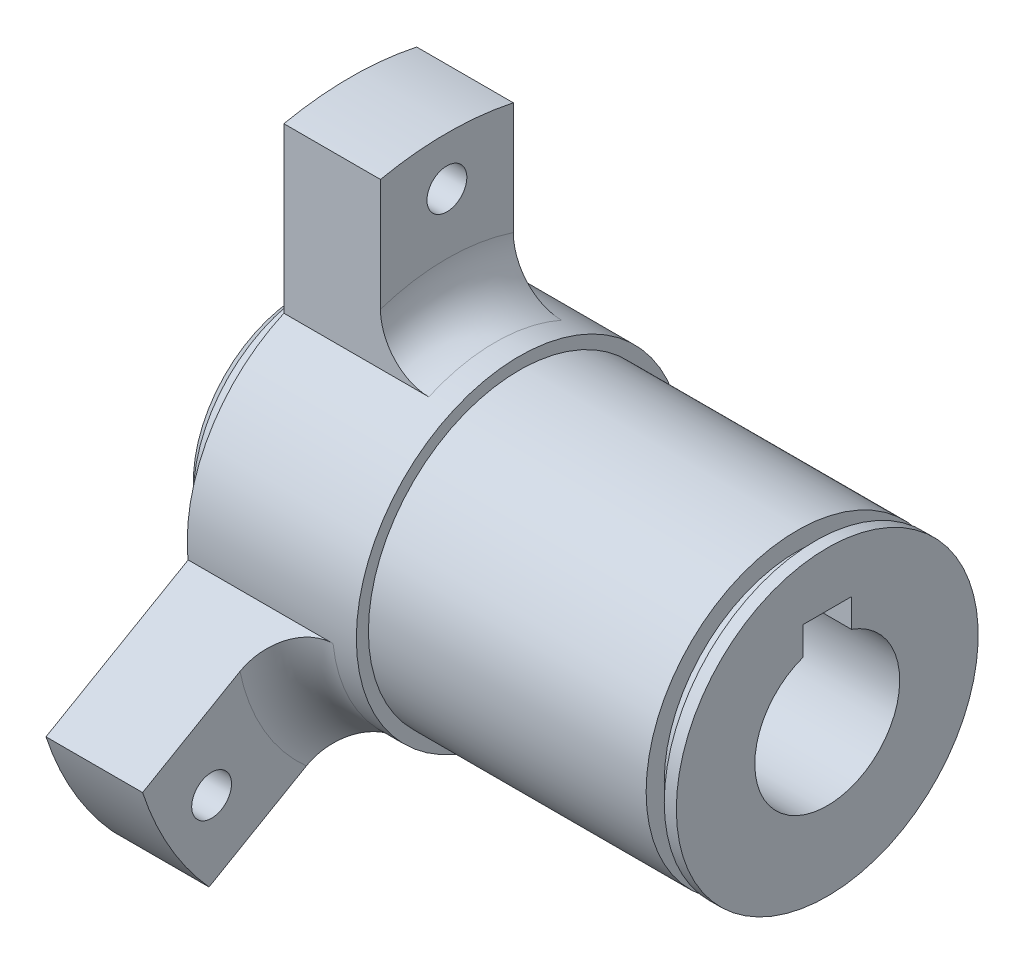
SolidWorks part; units mm, degrees
material "1060 合金"
ref_plane "前视基准面" through (0, 0, 0) normal (0, 0, 1) x (1, 0, 0)
ref_plane "上视基准面" through (0, 0, 0) normal (0, 1, 0) x (1, 0, 0)
ref_plane "右视基准面" through (0, 0, 0) normal (1, 0, 0) x (0, 0, -1)
sketch "草图2" plane through (0, 0, 0) normal (0, 0, 1) x (1, 0, 0)
  line L0 (0, 0) -> (170.3744, 0) construction
  line L2 (0, 0) -> (10, 0)
  line L3 (0, 10) -> (0, 26.5)
  line L4 (0, 26.5) -> (8, 26.5)
  line L5 (8, 13.5) -> (8, 26.5)
  line L6 (10, 0) -> (39.5, 0)
  line L7 (0, 0) -> (-4, 0)
  line L8 (14, 12.5) -> (39.5, 12.5)
  line L9 (39.5, 0) -> (39.5, 12.5)
  line L11 (8, 13.5) -> (14, 13.5)
  line L12 (14, 12.5) -> (14, 13.5)
  line L13 (0, 10) -> (-4, 10)
  line L14 (-4, 0) -> (-4, 10)
  dimension "D1" = 26.5
  dimension "D2" = 8
  dimension "D3" = 6
  dimension "D4" = 12.5
  dimension "D5" = 1
  dimension "D6" = 25.5
  dimension "D7" = 10
  dimension "D8" = 4
revolve "旋转1" add sketch "草图2" angle 360 about L0
sketch "草图3" plane through (39.5, 0, 0) normal (1, 0, 0) x (0, 0, -1)
  line L0 (0, 0) -> (0, 22.0591) construction
  line L3 (-2, 5.6569) -> (-2, 8)
  line L4 (-2, 8) -> (2, 8)
  line L5 (2, 5.6569) -> (2, 8)
  line L6 (-2.2567, 3.7433) -> (2, 8) construction
  line L7 (-2, 8) -> (2.2567, 3.7433) construction
  arc A0 (-2, 5.6569) -> (2, 5.6569) centre (0, 0) ccw
  point P3 (0, 6)
  dimension "D1" = 12
  dimension "D2" = 4
  dimension "D3" = 8
extrude "键槽轴孔" cut sketch "草图3" against normal through all
sketch "草图8" plane through (0, 0, 0) normal (0, 1, 0) x (1, 0, 0)
  line L0 (0, 0) -> (67.4134, 0) construction
  line L1 (39.5, 12.5) -> (14, 12.5) construction
  line L2 (37, 12.5) -> (38.5, 12.5)
  line L3 (37, 12.5) -> (37, 11)
  line L4 (37, 11) -> (38.5, 11)
  line L5 (38.5, 12.5) -> (38.5, 11)
  line L6 (39.5, -12.5) -> (39.5, 12.5) construction
  dimension "D1" = 1
  dimension "D2" = 1.5
  dimension "D3" = 1.5
revolve "卡簧槽" cut sketch "草图8" angle 360 about L0
hole_wizard "M4 螺纹孔1" positions "草图5" profile "草图4" tap size "M4" standard "GB"
sketch "草图5" plane through (0, 0, 0) normal (-1, 0, 0) x (0, 0, 1)
  line L0 (0, 0) -> (0, 25.1605) construction
  circle A0 centre (0, 0) radius 22.5
  point P0 (0, 22.5)
  point P36 (19.4856, -11.25)
  point P37 (-19.4856, -11.25)
  dimension "D1" = 45
  dimension "D2" = 3
sketch "草图4" plane through (0, 22.5, 0) normal (0, 1, 0) x (0, 0, 1)
  line L0 (0, 0) -> (0, 11.0914)
  line L1 (0, 11.0914) -> (1.65, 10.1)
  line L2 (1.65, 10.1) -> (1.65, 0)
  line L5 (1.65, 0) -> (0, 0)
  line L10 (0, 11.0914) -> (-1.65, 10.1) construction
  line L11 (0, -6.35) -> (0, 107.95) construction
  dimension "螺纹孔钻头直径" = 3.3
  dimension "螺纹孔钻头深度" = 10.1
  dimension "导头角度" = 118
cosmetic thread "孔螺蚊线1" parameters "D1"=8, "D2"=4
cosmetic thread "孔螺蚊线2" parameters "D1"=8, "D2"=4
cosmetic thread "孔螺蚊线3" parameters "D1"=8, "D2"=4
fillet "圆角1" radius 4 1 edges at (8, 0, 13.5)
sketch "草图13" plane through (0, 0, 0) normal (-1, 0, 0) x (0, 0, 1)
  line L0 (0, 31.1882) -> (0, 0) construction
  line L1 (-5.5, 12.3288) -> (-5.5, 25.923)
  line L2 (5.5, 12.3288) -> (5.5, 25.923)
  line L3 (13.4271, -1.4013) -> (25.1999, -8.1983)
  line L4 (7.9271, -10.9276) -> (19.6999, -17.7246)
  line L5 (-7.9271, -10.9276) -> (-19.6999, -17.7246)
  line L6 (-13.4271, -1.4013) -> (-25.1999, -8.1983)
  circle A1 centre (0, 0) radius 26.5 construction
  circle A3 centre (0, 0) radius 13.5 construction
  arc A4 (-5.5, 25.923) -> (-25.1999, -8.1983) centre (0, 0) ccw
  arc A5 (-5.5, 12.3288) -> (-13.4271, -1.4013) centre (0, 0) ccw
  arc A6 (13.4271, -1.4013) -> (5.5, 12.3288) centre (0, 0) ccw
  arc A7 (25.1999, -8.1983) -> (5.5, 25.923) centre (0, 0) ccw
  arc A8 (-19.6999, -17.7246) -> (19.6999, -17.7246) centre (0, 0) ccw
  arc A9 (-7.9271, -10.9276) -> (7.9271, -10.9276) centre (0, 0) ccw
  dimension "D1" = 11
extrude "切除-拉伸2" cut sketch "草图13" against normal up to next
chamfer "倒角1" distance 1 angle 45 1 edges at (-4, 0, 10)
